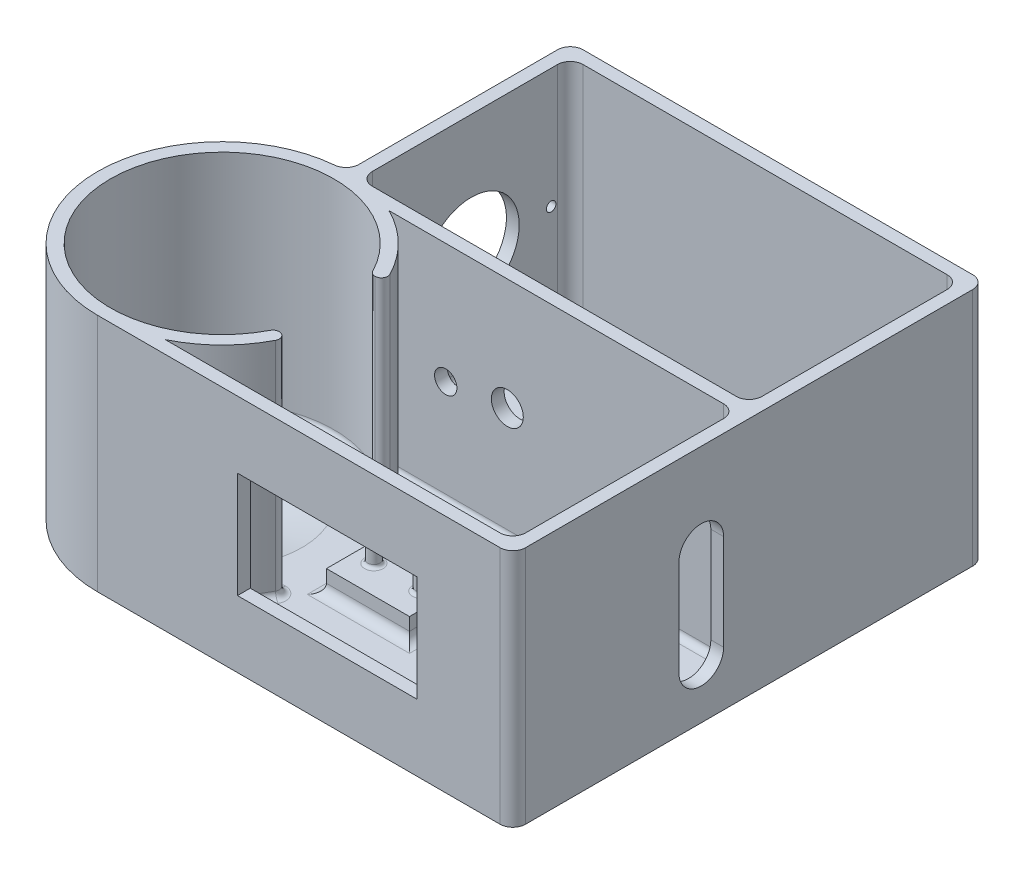
SolidWorks part; units mm, degrees
ref_plane "Front Plane" through (0, 0, 0) normal (0, 0, 1) x (1, 0, 0)
ref_plane "Top Plane" through (0, 0, 0) normal (0, 1, 0) x (1, 0, 0)
ref_plane "Right Plane" through (0, 0, 0) normal (1, 0, 0) x (0, 0, -1)
sketch "Sketch1" plane through (0, 0, 0) normal (0, 1, 0) x (1, 0, 0)
  line L1 (-65, -39) -> (65, -39)
  line L2 (-65, -39) -> (-65, 39) construction
  line L3 (-65, 39) -> (65, 39)
  line L4 (65, -39) -> (65, 39)
  line L5 (0, 39) -> (0, -39) construction
  line L6 (-65, 0) -> (65, 0) construction
  arc A0 (-65, 39) -> (-65, -39) centre (-65, 0) ccw
  circle A1 centre (-65, 0) radius 5
  point P0 (0, 0)
  dimension "D3" = 10
  dimension "D1" = 78
  dimension "D2" = 130
extrude "Boss-Extrude1" add sketch "Sketch1" along normal blind 5
sketch "Sketch3" plane through (0, 5, 0) normal (0, 1, 0) x (1, 0, 0)
  line L3 (61, 35) -> (-65, 35)
  line L4 (-65, -35) -> (61, -35)
  line L5 (61, -35) -> (61, 35)
  line L9 (65, -39) -> (65, 39)
  line L10 (65, 39) -> (-65, 39)
  line L11 (-65, -39) -> (65, -39)
  line L12 (65, -39) -> (65, 39)
  line L13 (65, 39) -> (-65, 39)
  line L14 (-65, -39) -> (65, -39)
  line L15 (-104, 0) -> (65, 0) construction
  line L16 (-47.7953, 35) -> (-65, 35)
  line L17 (-33.3772, 15) -> (-29, 15)
  line L18 (-33.3772, -15) -> (-29, -15)
  arc A5 (-65, 35) -> (-65, -35) centre (-65, 0) ccw
  arc A6 (-65, 39) -> (-65, -39) centre (-65, 0) ccw
  arc A7 (-65, 39) -> (-65, -39) centre (-65, 0) ccw
  arc A8 (-33.3772, 15) -> (-33.3772, -15) centre (-65, 0) ccw
  arc A10 (-29, 15) -> (-29, -15) centre (-65, 0) ccw
  line M9 (65, -39) -> (65, 39)
  line M10 (65, 39) -> (-65, 39)
  arc M11 (-65, 39) -> (-65, -39) centre (-65, 0) ccw
  line M12 (-65, -39) -> (65, -39)
  dimension "D3" = 15
  dimension "D4" = 15
  dimension "D1" = 0
  dimension "D2" = 4
extrude "Boss-Extrude3" add sketch "Sketch3" along normal blind 70 contours A5 L3 A10 M11 | A10 L3 A8 | L4 A10 A8 | A10 L4 A8 | L5 L4 A10 M12 M9 | L5 A10 L3 M10 region at (6.6023, 5, -36.516) region at (-41.1908, 5, -26.653) region at (-56.3977, 5, -35.9614) region at (-41.1908, 5, 26.653)
sketch "Sketch4" plane through (0, 0, 39) normal (0, 0, 1) x (1, 0, 0)
  line L1 (-21.2, 54.1) -> (35, 54.1)
  line L2 (-21.2, 54.1) -> (-21.2, 20.9)
  line L3 (-21.2, 20.9) -> (35, 20.9)
  line L4 (35, 54.1) -> (35, 20.9)
  line L5 (6.9, 20.9) -> (6.9, 54.1) construction
  line L6 (-21.2, 37.5) -> (35, 37.5) construction
  line L8 (65, 75) -> (65, 0) construction
  point P0 (6.9, 37.5)
  point P10 (65, 37.5)
  dimension "D1" = 56.2
  dimension "D2" = 33.2
  dimension "D3" = 30
extrude "Cut-Extrude1" cut sketch "Sketch4" against normal up to next
sketch "Sketch5" plane through (0, 0, -39) normal (0, 0, -1) x (-1, 0, 0)
  line L0 (-65, 75) -> (-65, 0) construction
  line L1 (65, 75) -> (65, 0) construction
  circle A0 centre (30, 37.5) radius 3.5
  point P2 (0, 0)
  point P5 (-65, 37.5)
  point P6 (0, 0)
  dimension "D1" = 7
  dimension "D2" = 35
extrude "Cut-Extrude3" cut sketch "Sketch5" against normal up to next
fillet "Fillet2" radius 2 4 edges at (-33.3772, 40, 15) (-33.3772, 40, -15) (-29, 40, 15) (-29, 40, -15)
chamfer "Chamfer1" distance 20 angle 15 1 edges at (-65, 5, 5) first distance on face at (-22.8419, 5, 0)
sketch "Sketch6" plane through (0, 5, 0) normal (0, 1, 0) x (1, 0, 0)
  line L0 (-65, 8.85) -> (-65, -8.85) construction
  line L1 (-77.5, 8.85) -> (2.5, 8.85)
  line L2 (-77.5, 8.85) -> (-77.5, -8.85)
  line L3 (-77.5, -8.85) -> (2.5, -8.85)
  line L4 (2.5, 8.85) -> (2.5, -8.85)
  line L5 (-37.5, -8.85) -> (-37.5, 8.85) construction
  line L6 (-77.5, 0) -> (2.5, 0) construction
  line L7 (-65, 6.3397) -> (-65, -6.3397) construction
  circle A0 centre (-57.5, 0) radius 1.9
  circle A1 centre (-72.5, 0) radius 1.9
  circle A3 centre (-65, 0) radius 6.3397 construction
  circle A4 centre (-17.5, 0) radius 1.9
  circle A5 centre (-2.5, 0) radius 1.9
  point P0 (-37.5, 0)
  dimension "D5" = 3.8
  dimension "D6" = 3.8
  dimension "D1" = 80
  dimension "D2" = 17.7
  dimension "D3" = 20
  dimension "D4" = 15
  dimension "D7" = 7.5
sketch "Sketch7" plane through (0, 5, 0) normal (0, 1, 0) x (1, 0, 0)
  line L0 (-77.5, -8.85) -> (2.5, -8.85) construction
  line L1 (2.5, 8.85) -> (-23.5, 8.85)
  line L2 (2.5, 8.85) -> (2.5, -8.85)
  line L3 (2.5, -8.85) -> (-23.5, -8.85)
  line L4 (-23.5, 8.85) -> (-23.5, -8.85)
  dimension "D1" = 26
extrude "Boss-Extrude4" add sketch "Sketch7" along normal blind 7
fillet "Fillet4" radius 3 4 edges at (-23.5, 5, 0) (-10.5, 5, -8.85) (2.5, 5, 0) (-10.5, 5, 8.85)
sketch "Sketch8" plane through (0, 12, 0) normal (0, 1, 0) x (1, 0, 0)
  circle A0 centre (-17.5, 0) radius 1.9
  circle A1 centre (-2.5, 0) radius 1.9
  circle A2 centre (-17.5, 0) radius 1.9 construction
  circle A3 centre (-2.5, 0) radius 1.9 construction
extrude "Boss-Extrude5" add sketch "Sketch8" along normal blind 5
fillet "Fillet5" radius 1 2 edges at (-2.5, 12, -1.9) (-17.5, 12, -1.9)
sketch "Sketch9" plane through (65, 0, 0) normal (1, 0, 0) x (0, 0, -1)
  line L0 (20, 47) -> (20, 17) construction
  line L1 (27, 47) -> (27, 17)
  line L2 (13, 47) -> (13, 17)
  line L3 (-39, 0) -> (39, 0) construction
  line L5 (39, 75) -> (39, 0) construction
  arc A0 (27, 47) -> (13, 47) centre (20, 47) ccw
  arc A1 (13, 17) -> (27, 17) centre (20, 17) ccw
  point P2 (20, 32)
  dimension "D2" = 7
  dimension "D3" = 17
  dimension "D1" = 30
  dimension "D4" = 19
extrude "Cut-Extrude4" cut sketch "Sketch9" against normal up to next
sketch "Sketch10" plane through (0, 0, 0) normal (0, 1, 0) x (1, 0, 0)
  line L0 (65, -39) -> (65, 39) construction
  line L1 (-65, 39) -> (65, 39)
  line L2 (-65, 39) -> (-65, 109)
  line L3 (-65, 109) -> (65, 109)
  line L4 (65, 39) -> (65, 109)
  dimension "D1" = 70
extrude "Boss-Extrude6" add sketch "Sketch10" along normal up to surface (5 mm away) up to face at (-10.5, 5, 0)
sketch "Sketch11" plane through (0, 5, 0) normal (0, 1, 0) x (1, 0, 0)
  line L0 (-61, 105) -> (-61, 43)
  line L1 (-61, 43) -> (61, 43)
  line L2 (61, 43) -> (61, 105)
  line L3 (61, 105) -> (-61, 105)
  line L4 (65, 109) -> (-65, 109)
  line L5 (-65, 109) -> (-65, 39)
  line L6 (-65, 39) -> (65, 39)
  line L7 (65, 39) -> (65, 109)
  line L8 (65, 109) -> (-65, 109)
  line L9 (-65, 109) -> (-65, 39)
  line L10 (-65, 39) -> (65, 39)
  line L11 (65, 39) -> (65, 109)
  line L12 (-61, 43) -> (-61, 39)
  line L13 (61, 43) -> (61, 39)
  line M9 (65, 109) -> (-65, 109)
  line M10 (-65, 109) -> (-65, 39)
  line M11 (-65, 39) -> (65, 39)
  line M12 (65, 39) -> (65, 109)
  dimension "D1" = 0
  dimension "D2" = 4
extrude "Boss-Extrude7" add sketch "Sketch11" along normal up to surface (70 mm away) contours L2 L13 L12 L0 L3 M11 M12 M9 M10 region at (-62.4765, 5, -74) up to face at (-9.75, 75, 0)
sketch "Sketch12" plane through (-65, 0, 0) normal (-1, 0, 0) x (0, 0, 1)
  line L0 (-74, 75) -> (-74, 0) construction
  line L1 (-109, 75) -> (-39, 75) construction
  line L2 (-109, 0) -> (-39, 0) construction
  circle A0 centre (-99, 37.5) radius 1.5
  circle A1 centre (-49, 37.5) radius 1.5
  circle A2 centre (-74, 37.5) radius 15
  point P8 (-74, 37.5)
  dimension "D2" = 3
  dimension "D3" = 30
  dimension "D1" = 25
extrude "Cut-Extrude5" cut sketch "Sketch12" against normal up to next
sketch "Sketch13" plane through (0, 5, 0) normal (0, 1, 0) x (1, 0, 0)
  line L0 (61, 39) -> (61, 105) construction
  circle A0 centre (21, 72) radius 12.5
  point P2 (0, 0)
  point P5 (61, 72)
  dimension "D2" = 25
  dimension "D1" = 40
extrude "Cut-Extrude6" cut sketch "Sketch13" against normal up to next
chamfer "Chamfer2" distance 20 angle 15 1 edges at (21, 5, -59.5) first distance on face at (21, 5, -59.5)
sketch "Sketch14" plane through (0, 0, -35) normal (0, 0, 1) x (1, 0, 0)
  line L1 (61, 75) -> (61, 5) construction
  circle A0 centre (-10.7202, 40) radius 5
  point P2 (0, 0)
  point P5 (0, 0)
  point P8 (61, 40)
  dimension "D1" = 10
extrude "Cut-Extrude7" cut sketch "Sketch14" against normal up to next
fillet "Fillet6" radius 4 10 edges at (61, 40, -105) (65, 37.5, -109) (-65, 37.5, -109) (-61, 40, -105) (61, 40, -35) (61, 40, 35) (65, 37.5, 39) (-61, 40, -39) (-65, 37.5, -39) (61, 40, -39)
fillet "Fillet7" radius 2 20 edges at (-59.8284, 5, -103.8284) (0, 5, -105) (59.8284, 5, -103.8284) (61, 5, -72) (59.8284, 5, -40.1716) (0, 5, -39) (-59.8284, 5, -40.1716) (-37.7071, 5, 27.8585) (-30.4282, 5, 15.9602) (-33.1764, 5, 15.2915) (-100, 5, 0) (-33.1764, 5, -15.2915) (-30.4282, 5, -15.9602) (4.6023, 5, 35) (59.8284, 5, 33.8284) (61, 5, 0) (59.8284, 5, -33.8284) (-61, 5, -72) (-37.7071, 5, -27.8585) (4.6023, 5, -35)
